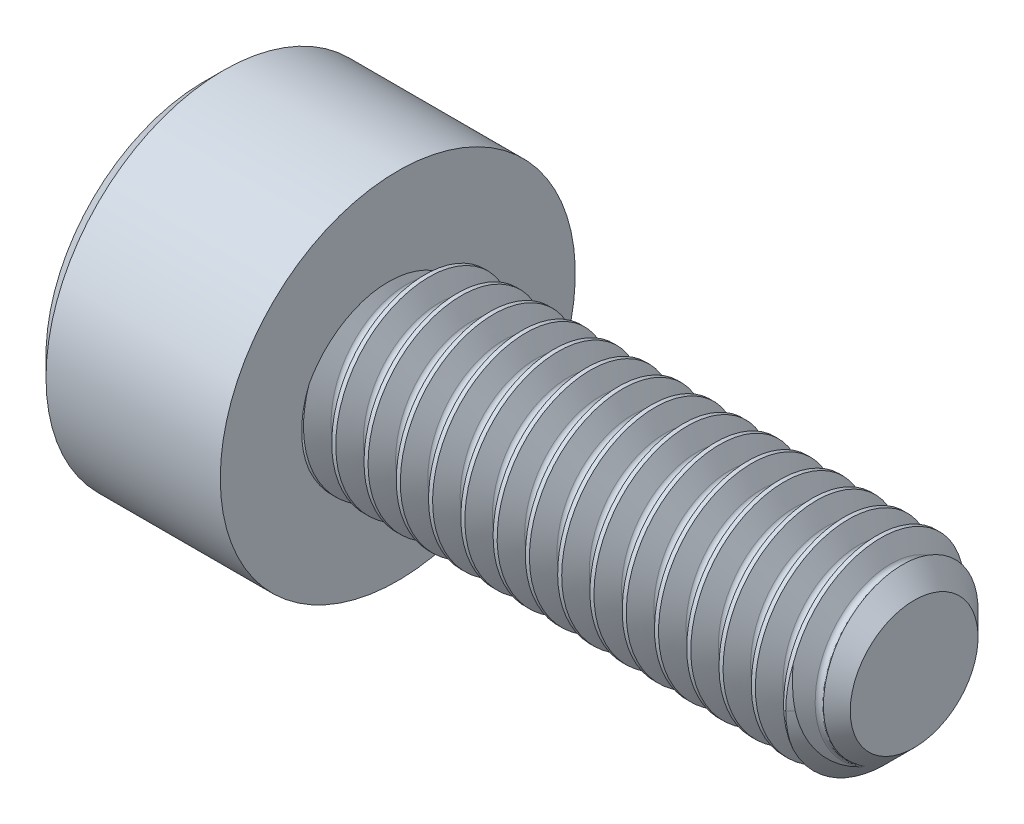
SolidWorks part; units mm, degrees
material "AISI Type 316L stainless steel"
ref_plane "Front Plane" through (0, 0, 0) normal (0, 0, 1) x (1, 0, 0)
ref_plane "Top Plane" through (0, 0, 0) normal (0, 1, 0) x (1, 0, 0)
ref_plane "Right Plane" through (0, 0, 0) normal (1, 0, 0) x (0, 0, -1)
sketch "Sketch1" plane through (0, 0, 0) normal (0, 0, 1) x (1, 0, 0)
  line L0 (-118.274, 0) -> (129.3083, 0) construction
  line L1 (0, 0) -> (0, 2.75)
  line L2 (0, 2.75) -> (3, 2.75)
  line L4 (11, 0) -> (11, 1.49)
  line L5 (11, 1.49) -> (3, 1.49)
  line L6 (3, 1.49) -> (3, 2.75)
  line L7 (0, 0) -> (11, 0)
  dimension "D1" = 8
  dimension "D2" = 1.49
  dimension "D3" = 2.75
  dimension "D4" = 3
revolve "Revolve1" add sketch "Sketch1" angle 360 about L0
chamfer "Chamfer1" distance 0.5 angle 45 1 edges at (11, 0, 1.49)
chamfer "Chamfer2" distance 0.3 angle 45 1 edges at (0, 0, 2.75)
sketch "Sketch3" plane through (0, 0, 0) normal (1, 0, 0) x (0, 0, -1)
  line L1 (-1.4434, 0) -> (-0.7217, -1.25)
  line L2 (-0.7217, -1.25) -> (0.7217, -1.25)
  line L3 (0.7217, -1.25) -> (1.4434, 0)
  line L4 (1.4434, 0) -> (0.7217, 1.25)
  line L5 (0.7217, 1.25) -> (-0.7217, 1.25)
  line L6 (-0.7217, 1.25) -> (-1.4434, 0)
  circle A0 centre (0, 0) radius 1.25 construction
extrude "Cut-Extrude1" cut sketch "Sketch3" along normal blind 2.5
chamfer "Chamfer3" distance 0.3 angle 45 6 edges at (0, 1.25, 0) (0, 0.625, 1.0825) (0, -0.625, 1.0825) (0, -1.25, 0) (0, -0.625, -1.0825) (0, 0.625, -1.0825)
sketch "Sketch5" plane through (11, 0, 0) normal (1, 0, 0) x (0, 0, -1)
  circle A0 centre (0, 0) radius 1.49
curve "Helix/Spiral1" pitch 0.5 height 8 radius 1.49 centre (11, 0, 0) axis (-1, 0, 0) start towards (0, 0, -1)
sketch "Sketch8" plane through (0, 0, 0) normal (0, 1, 0) x (1, 0, 0)
  line L0 (11, 1.49) -> (11, 1.1111) construction
  line L1 (11.0625, 1.2194) -> (11.3281, 1.6794)
  line L2 (11.3281, 1.6794) -> (10.6719, 1.6794)
  line L3 (10.6719, 1.6794) -> (10.9375, 1.2194)
  circle A0 centre (11, 1.49) radius 0.1894 construction
  arc A1 (11.0625, 1.2194) -> (10.9375, 1.2194) centre (11, 1.2555) cw
  point P10 (12.9236, 0.631)
  point P11 (-69293.6671, 500000)
  point P12 (-69293.3055, 500000)
  dimension "D2" = 0.0722
  dimension "D1" = 0.3789
sweep "Cut-Sweep1" cut profiles "Sketch8" path "Helix/Spiral1" align with end faces yes
